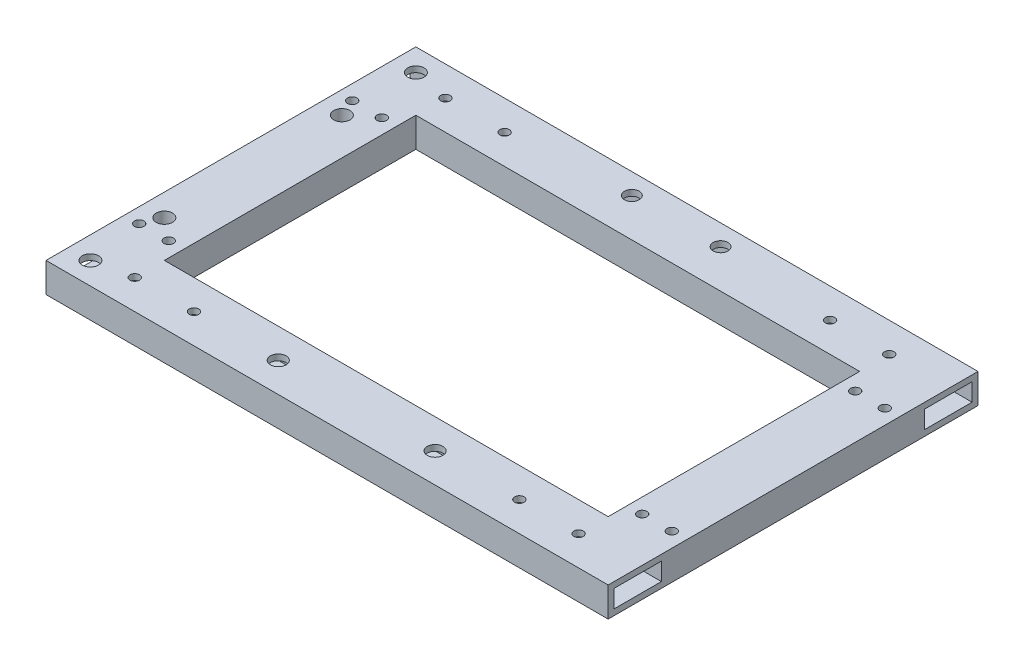
SolidWorks part; units mm, degrees
ref_plane "前视基准面" through (0, 0, 0) normal (0, 0, 1) x (1, 0, 0)
ref_plane "上视基准面" through (0, 0, 0) normal (0, 1, 0) x (1, 0, 0)
ref_plane "右视基准面" through (0, 0, 0) normal (1, 0, 0) x (0, 0, -1)
sketch "Sketch1" plane through (0, 0, 0) normal (0, 1, 0) x (1, 0, 0)
  line L1 (-95, -62.5) -> (95, -62.5)
  line L2 (-95, -62.5) -> (-95, 62.5)
  line L3 (-95, 62.5) -> (95, 62.5)
  line L4 (95, -62.5) -> (95, 62.5)
  line L5 (-95, -62.5) -> (95, 62.5) construction
  line L6 (-95, 62.5) -> (95, -62.5) construction
  line L7 (-75, -42.5) -> (75, -42.5)
  line L8 (-75, -42.5) -> (-75, 42.5)
  line L9 (-75, 42.5) -> (75, 42.5)
  line L10 (75, -42.5) -> (75, 42.5)
  line L11 (-75, -42.5) -> (75, 42.5) construction
  line L12 (-75, 42.5) -> (75, -42.5) construction
  point P0 (0, 0)
  point P6 (0, 0)
  dimension "D1" = 20
  dimension "D2" = 20
  dimension "D3" = 150
  dimension "D4" = 85
extrude "Extrude1" add sketch "Sketch1" along normal blind 10
sketch "Sketch2" plane through (-95, 0, 0) normal (-1, 0, 0) x (0, 0, 1)
  line L0 (0, 0) -> (0, 10) construction
  line L1 (-60.5, 8) -> (-44.5, 8)
  line L2 (-60.5, 8) -> (-60.5, 2)
  line L3 (-60.5, 2) -> (-44.5, 2)
  line L4 (-44.5, 8) -> (-44.5, 2)
  line L5 (-62.5, 10) -> (62.5, 10) construction
  line L6 (-62.5, 10) -> (-62.5, 0) construction
  line L7 (-62.5, 0) -> (62.5, 0) construction
  line L8 (44.5, 8) -> (44.5, 2)
  line L9 (60.5, 2) -> (44.5, 2)
  line L10 (60.5, 8) -> (60.5, 2)
  line L11 (60.5, 8) -> (44.5, 8)
  dimension "D1" = 2
  dimension "D2" = 2
  dimension "D3" = 2
  dimension "D4" = 16
extrude "Cut-Extrude1" cut sketch "Sketch2" against normal blind 200
sketch "Sketch3" plane through (0, 10, 0) normal (0, 1, 0) x (1, 0, 0)
  circle A0 centre (75, -52.5) radius 1.6 construction
  circle A1 centre (55, -52.5) radius 1.6 construction
  circle A2 centre (75, 52.5) radius 1.6 construction
  circle A3 centre (55, 52.5) radius 1.6 construction
  circle A4 centre (-55, 52.5) radius 1.6 construction
  circle A5 centre (-75, 52.5) radius 1.6 construction
  circle A6 centre (-75, -52.5) radius 1.6 construction
  circle A7 centre (-55, -52.5) radius 1.6 construction
  circle A8 centre (26.5, -52.5) radius 2.65 construction
  circle A9 centre (-26.5, -52.5) radius 2.65 construction
  circle A10 centre (15, 55.5) radius 2.5 construction
  circle A11 centre (-15, 55.5) radius 2.5 construction
  circle A12 centre (75, -52.5) radius 1.6
  circle A13 centre (55, -52.5) radius 1.6
  circle A14 centre (75, 52.5) radius 1.6
  circle A15 centre (55, 52.5) radius 1.6
  circle A16 centre (-55, 52.5) radius 1.6
  circle A17 centre (-75, 52.5) radius 1.6
  circle A18 centre (-75, -52.5) radius 1.6
  circle A19 centre (-55, -52.5) radius 1.6
  circle A20 centre (26.5, -52.5) radius 2.65
  circle A21 centre (-26.5, -52.5) radius 2.65
  circle A22 centre (15, 55.5) radius 2.5
  circle A23 centre (-15, 55.5) radius 2.5
extrude "Cut-Extrude2" cut sketch "Sketch3" against normal blind 20
sketch "Sketch4" plane through (0, 13, 0) normal (0, 1, 0) x (1, 0, 0)
  circle A4 centre (90, 36) radius 1.6
  circle A5 centre (80, 36) radius 1.6
  circle A6 centre (90, -36) radius 1.6
  circle A7 centre (80, -36) radius 1.6
  circle A8 centre (-80, -36) radius 1.6 construction
  circle A9 centre (-90, -36) radius 1.6 construction
  circle A10 centre (-80, 36) radius 1.6 construction
  circle A11 centre (-90, 36) radius 1.6 construction
  circle A12 centre (-80, -36) radius 1.6
  circle A13 centre (-90, -36) radius 1.6
  circle A14 centre (-80, 36) radius 1.6
  circle A15 centre (-90, 36) radius 1.6
extrude "Cut-Extrude3" cut sketch "Sketch4" against normal blind 26
sketch "Sketch5" plane through (0, 10, 0) normal (0, 1, 0) x (1, 0, 0)
  circle A0 centre (-87.5, -55) radius 2.75 construction
  circle A1 centre (-87.5, -30) radius 2.75 construction
  circle A2 centre (-87.5, 30) radius 2.75 construction
  circle A3 centre (-87.5, 55) radius 2.75 construction
  circle A4 centre (-87.5, -55) radius 2.75
  circle A5 centre (-87.5, -30) radius 2.75
  circle A6 centre (-87.5, 30) radius 2.75
  circle A7 centre (-87.5, 55) radius 2.75
extrude "Cut-Extrude4" cut sketch "Sketch5" against normal blind 10
